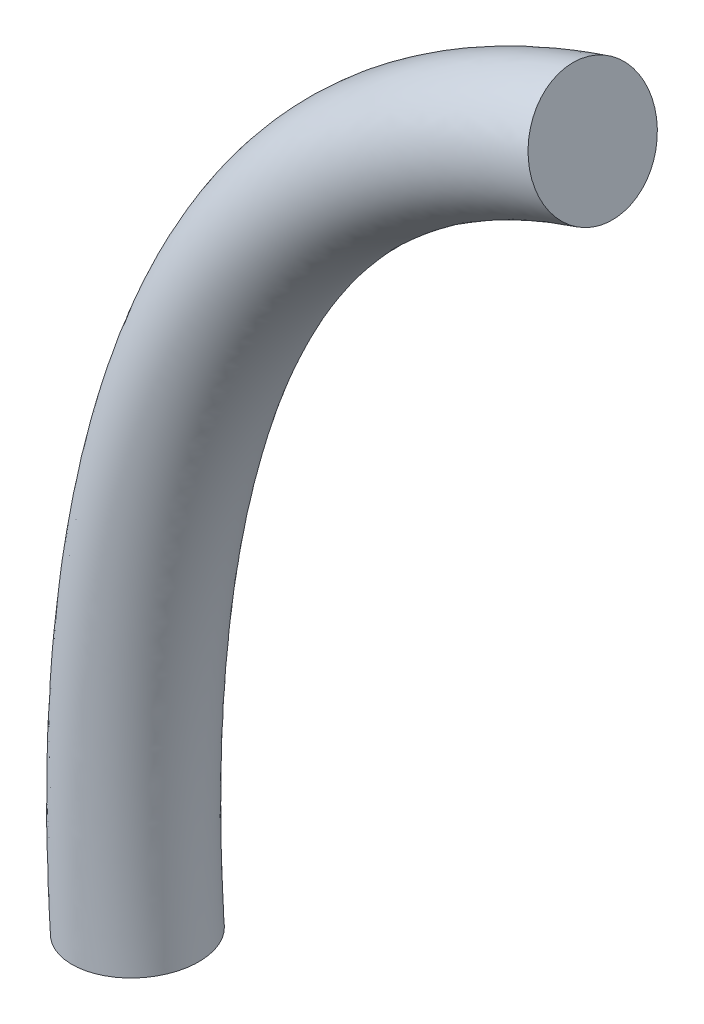
SolidWorks part; units mm, degrees
ref_plane "Front Plane" through (0, 0, 0) normal (0, 0, 1) x (1, 0, 0)
ref_plane "Top Plane" through (0, 0, 0) normal (0, 1, 0) x (1, 0, 0)
ref_plane "Right Plane" through (0, 0, 0) normal (1, 0, 0) x (0, 0, -1)
sketch "Sketch16" plane through (0, 0, 0) normal (0, 0, 1) x (1, 0, 0)
  spline S0 degree 3 poles (0, 0) (-1.197, 18.1744) (2.9453, 40.0757) (23.4695, 46.99) knots 0 0 0 0 1 1 1 1
  dimension "D1" = 46.99
  dimension "D2" = 5.0129
  dimension "D3" = 23.4695
  dimension "D4" = 11.0512
  dimension "D5" = 30.875
sweep "Sweep2" add path "Sketch16" circular profile diameter 6.35 parameters "D3"=6.35
